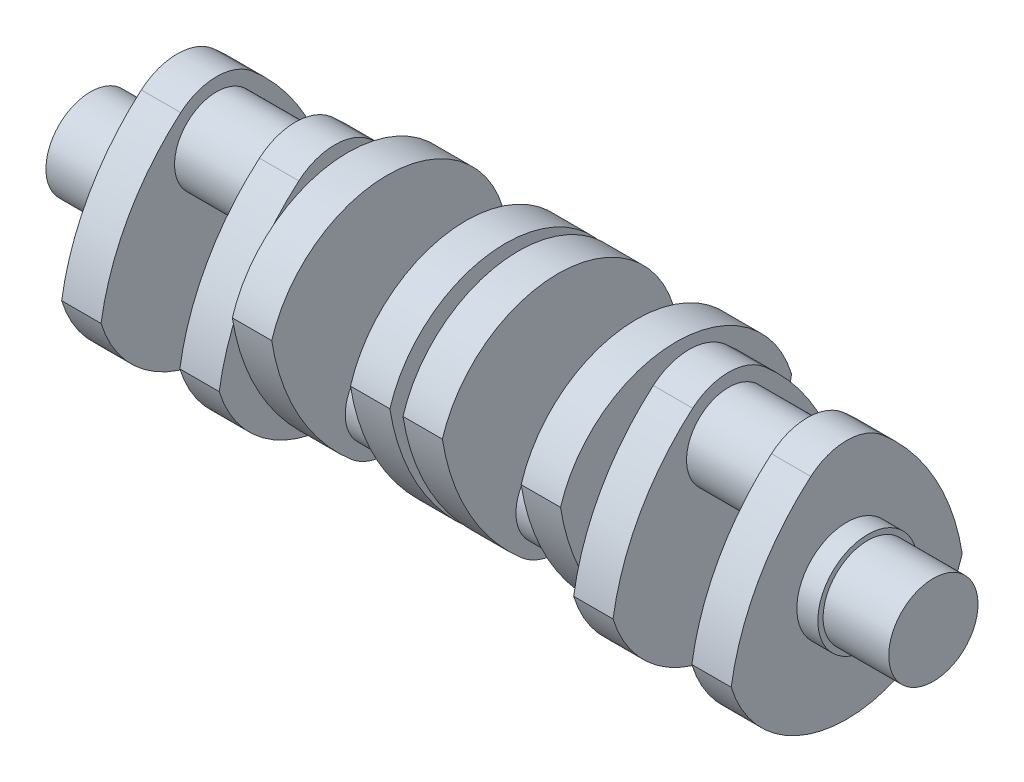
SolidWorks part; units mm, degrees
ref_plane "Front Plane" through (0, 0, 0) normal (0, 0, 1) x (1, 0, 0)
ref_plane "Top Plane" through (0, 0, 0) normal (0, 1, 0) x (1, 0, 0)
ref_plane "Right Plane" through (0, 0, 0) normal (1, 0, 0) x (0, 0, -1)
sketch "Sketch1" plane through (0, 0, 0) normal (1, 0, 0) x (0, 0, -1)
  circle A0 centre (0, 0) radius 19
  circle A1 centre (0, 0) radius 17
  dimension "D1" = 38
  dimension "D2" = 34
extrude "Boss-Extrude1" add sketch "Sketch1" against normal blind 25 contours A1
extrude "Boss-Extrude2" add sketch "Sketch1<3>" along normal blind 8 contours A0
sketch "Sketch1<3>" plane through (0, 0, 0) normal (1, 0, 0) x (0, 0, -1) same geometry as "Sketch1"
sketch "Sketch2" plane through (8, 0, 0) normal (1, 0, 0) x (0, 0, -1)
  arc A0 (-13.6681, 40.9431) -> (13.6681, 40.9431) centre (0, 25) cw
  arc A1 (44, -13.4164) -> (-44, -13.4164) centre (0, 0) cw
  arc A2 (-13.6681, 40.9431) -> (-44, -13.4164) centre (44.9095, -27.3845) ccw
  arc A3 (13.6681, 40.9431) -> (44, -13.4164) centre (-44.9095, -27.3845) cw
  dimension "D3" = 46
  dimension "D4" = 21
  dimension "D5" = 90
  dimension "D6" = 90
  dimension "D1" = 25
  dimension "D2" = 88
extrude "Boss-Extrude3" add sketch "Sketch2" along normal blind 15
sketch "Sketch4" plane through (23, 0, 0) normal (1, 0, 0) x (0, 0, -1)
  circle A0 centre (0, 25) radius 16
  dimension "D1" = 32
extrude "Boss-Extrude4" add sketch "Sketch4" along normal blind 15
mirror "Mirror1" about plane through (38, 25, 0) normal (1, 0, 0) of "Boss-Extrude4", "Boss-Extrude3"
sketch "Sketch5" plane through (68, 0, 0) normal (1, 0, 0) x (0, 0, -1)
  circle A0 centre (0, 0) radius 17
  dimension "D1" = 34
extrude "Boss-Extrude5" add sketch "Sketch5" along normal blind 5
sketch "Sketch6" plane through (73, 0, 0) normal (1, 0, 0) x (0, 0, -1)
  circle A0 centre (0, 0) radius 17 construction
  arc A8 (-13.6681, -40.9431) -> (13.6681, -40.9431) centre (0, -25) ccw
  arc A9 (-44, 13.4164) -> (-13.6681, -40.9431) centre (44.9095, 27.3845) ccw
  arc A10 (44, 13.4164) -> (-44, 13.4164) centre (0, 0) ccw
  arc A11 (13.6681, -40.9431) -> (44, 13.4164) centre (-44.9095, 27.3845) ccw
  dimension "D1" = 21
  dimension "D2" = 90
  dimension "D3" = 46
  dimension "D4" = 13.6681
  dimension "D5" = 44
extrude "Boss-Extrude6" add sketch "Sketch6" along normal blind 15
sketch "Sketch7" plane through (88, 0, 0) normal (1, 0, 0) x (0, 0, -1)
  circle A0 centre (0, -25) radius 16
  dimension "D1" = 32
  dimension "D2" = 25
extrude "Boss-Extrude7" add sketch "Sketch7" along normal blind 30
sketch "Sketch8" plane through (118, 0, 0) normal (1, 0, 0) x (0, 0, -1)
  arc A4 (-13.6681, -40.9431) -> (13.6681, -40.9431) centre (0, -25) ccw
  arc A5 (13.6681, -40.9431) -> (44, 13.4164) centre (-44.9095, 27.3845) ccw
  arc A6 (44, 13.4164) -> (-44, 13.4164) centre (0, 0) ccw
  arc A7 (-44, 13.4164) -> (-13.6681, -40.9431) centre (44.9095, 27.3845) ccw
  arc A8 (-13.6681, -40.9431) -> (13.6681, -40.9431) centre (0, -25) ccw
  arc A9 (13.6681, -40.9431) -> (44, 13.4164) centre (-44.9095, 27.3845) ccw
  arc A10 (44, 13.4164) -> (-44, 13.4164) centre (0, 0) ccw
  arc A11 (-44, 13.4164) -> (-13.6681, -40.9431) centre (44.9095, 27.3845) ccw
  dimension "D1" = 0
extrude "Boss-Extrude8" add sketch "Sketch8" along normal blind 15
sketch "Sketch9" plane through (133, 0, 0) normal (1, 0, 0) x (0, 0, -1)
  circle A0 centre (0, 0) radius 17
  dimension "D1" = 34
extrude "Boss-Extrude9" add sketch "Sketch9" along normal blind 2.5
mirror "Mirror2" about plane through (135.5, 0, 0) normal (1, 0, 0) of bodies 110
